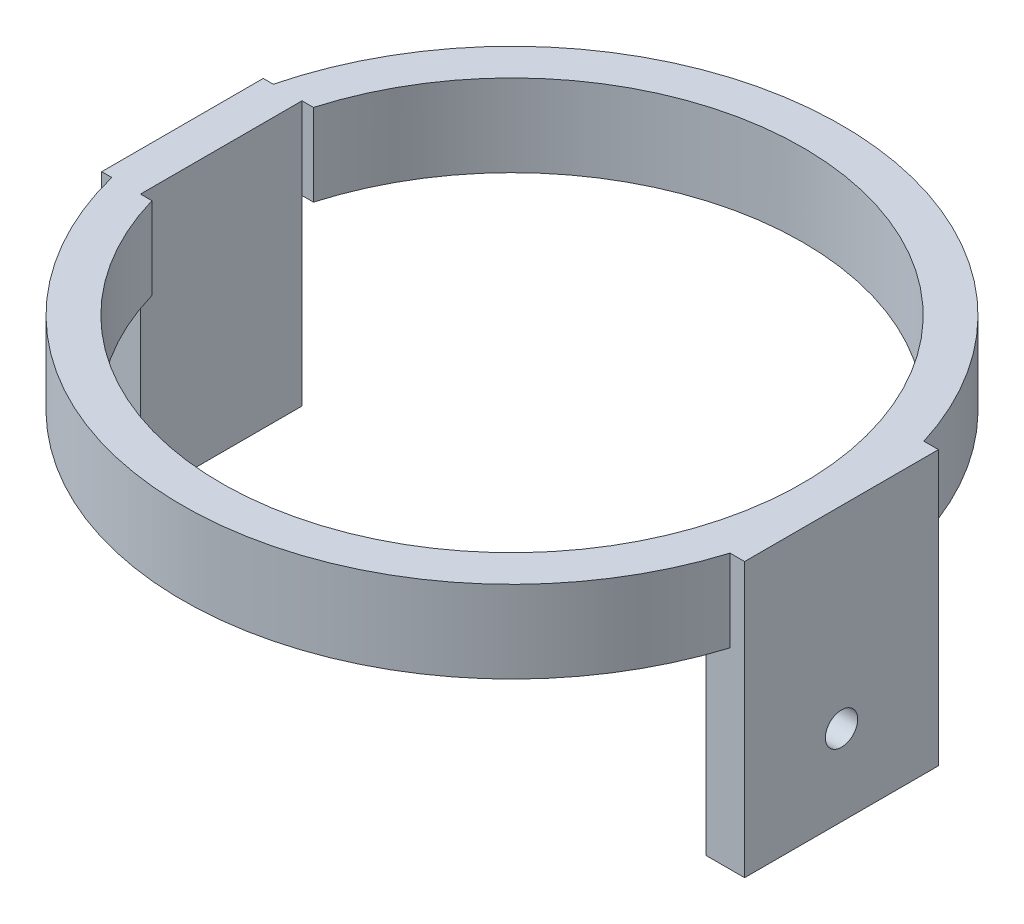
SolidWorks part; units mm, degrees
ref_plane "Front Plane" through (0, 0, 0) normal (0, 0, 1) x (1, 0, 0)
ref_plane "Top Plane" through (0, 0, 0) normal (0, 1, 0) x (1, 0, 0)
ref_plane "Right Plane" through (0, 0, 0) normal (1, 0, 0) x (0, 0, -1)
sketch "Sketch1" plane through (0, 0, 0) normal (0, 1, 0) x (1, 0, 0)
  circle A0 centre (0, 0) radius 102
  circle A1 centre (0, 0) radius 90
  dimension "D1" = 12
  dimension "D2" = 180
extrude "Boss-Extrude1" add sketch "Sketch1" against normal blind 25.4
ref_plane "Plane2" through (-90, 0, 0) normal (1, 0, 0) x (0, 0, -1)
sketch "Sketch6" plane through (-90, 0, 0) normal (1, 0, 0) x (0, 0, -1)
  line L0 (0, 0) -> (0, -59.7705)
  line L1 (102, 0) -> (-102, 0) construction
  point P4 (0, -107.9011)
  point P5 (0, 0)
  point P6 (0, -76.6926)
  dimension "D1" = 59.7705
sketch "Sketch7" plane through (-90, 0, 0) normal (1, 0, 0) x (0, 0, -1)
  line L0 (-90, -25.4) -> (90, -25.4) construction
  line L1 (-90, -25.4) -> (90, -25.4) construction
  line L2 (0, -81.8336) -> (0, -59.7705) construction
  line L3 (-25, -25.4) -> (25, -25.4) construction
  line L4 (-25, -25.4) -> (-25, -81.8336)
  line L5 (-25, -81.8336) -> (25, -81.8336)
  line L6 (25, -25.4) -> (25, -81.8336)
  line L7 (90, 0) -> (-90, 0) construction
  line L8 (90, 0) -> (-90, 0) construction
  line L10 (-25, -25.4) -> (25, -25.4) construction
  line L11 (-25, -25.4) -> (-25, 0)
  line L12 (-25, 0) -> (25, 0)
  line L13 (25, -25.4) -> (25, 0)
  point P2 (0, -59.7705)
  dimension "D1" = 22.0631
  dimension "D2" = 50
ref_plane "Plane3" through (-102, 0, 0) normal (-1, 0, 0) x (0, 0, 1)
extrude "Boss-Extrude4" add sketch "Sketch7" against normal up to surface (12 mm away) contours L6 L5 L4 L11 L12 L13 up to plane "Plane3"
sketch "Sketch14" plane through (0, -25.4, 0) normal (0, -1, 0) x (1, 0, 0)
  line L0 (-90, 25) -> (-86.4581, 25)
  line L1 (-86.4581, 25) -> (-86.4581, -25)
  line L2 (-86.4581, -25) -> (-90, -25)
  line L3 (-90, 25) -> (-90, -25)
  circle A0 centre (0, 0) radius 90 construction
extrude "Cut-Extrude2" cut sketch "Sketch14" against normal up to surface (25.4 mm away) up to face at (0, 0, 90)
ref_axis "Axis2" through (-90.6006, -59.7705, 0) along (1, 0, 0)
ref_plane "Plane4" through (90, 0, 0) normal (-1, 0, 0) x (0, 0, 1)
ref_plane "Plane5" through (102, 0, 0) normal (1, 0, 0) x (0, 0, -1)
sketch "Sketch8" plane through (90, 0, 0) normal (-1, 0, 0) x (0, 0, 1)
  line L0 (0, 0) -> (0, -84.7705) construction
  line L2 (-30, 0) -> (30, 0)
  line L3 (-30, 0) -> (-30, -84.7705)
  line L4 (-30, -84.7705) -> (30, -84.7705)
  line L5 (30, 0) -> (30, -84.7705)
  line L6 (90, 0) -> (-90, 0) construction
  line L7 (90, 0) -> (-90, 0) construction
  point P0 (0, -59.7705)
  dimension "D1" = 25
  dimension "D2" = 60
extrude "Boss-Extrude5" add sketch "Sketch8" against normal up to surface (12 mm away) contours L3 L4 L5 L2 up to plane "Plane5"
sketch "Sketch10" plane through (90, 0, 0) normal (-1, 0, 0) x (0, 0, 1)
  point P0 (0, -59.7705)
hole_wizard "M8 Clearance Hole1" positions "Sketch12" profile "Sketch13" hole size "M8" standard "ANSI Metric" end condition up to next
sketch "Sketch12" plane through (90, 0, 0) normal (-1, 0, 0) x (0, 0, 1)
  point P0 (0, -59.7705)
sketch "Sketch13" plane through (90, -59.7705, 0) normal (0, 1, 0) x (0, 0, 1)
  line L0 (0, 0) -> (0, 12)
  line L1 (0, 12) -> (5, 12)
  line L2 (5, 12) -> (5, 0)
  line L5 (5, 0) -> (0, 0)
  line L11 (0, -6.35) -> (0, 107.95) construction
  dimension "Thru Hole Dia." = 10
  dimension "Thru Hole Depth" = 12
ref_axis "Axis3" through (0, -21.2693, 0) along (0, 1, 0)
ref_point "Point1"
